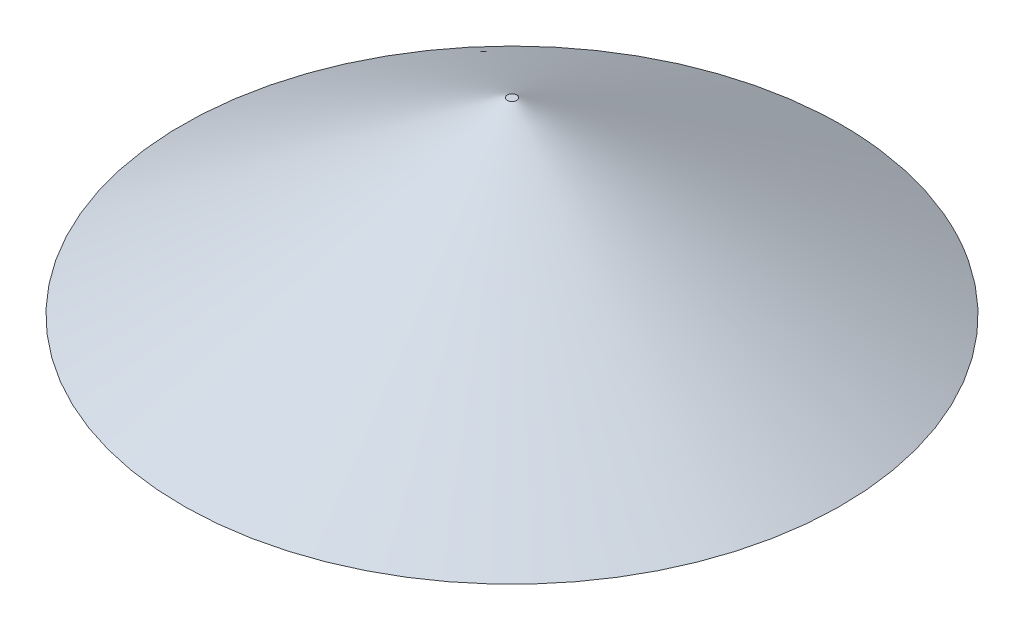
SolidWorks part; units mm, degrees
ref_plane "Front Plane" through (0, 0, 0) normal (0, 0, 1) x (1, 0, 0)
ref_plane "Top Plane" through (0, 0, 0) normal (0, 1, 0) x (1, 0, 0)
ref_plane "Right Plane" through (0, 0, 0) normal (1, 0, 0) x (0, 0, -1)
ref_plane "Plane1" through (0, 20, 0) normal (0, 1, 0) x (1, 0, 0)
sketch "Sketch1" plane through (0, 0, 0) normal (0, 1, 0) x (1, 0, 0)
  circle A0 centre (0, 0) radius 35
  dimension "D1" = 70
sketch "Sketch2" plane through (0, 20, 0) normal (0, 1, 0) x (1, 0, 0)
  circle A0 centre (0, 0) radius 0.5
loft "Loft1" add profiles "Sketch1", "Sketch2" connector at (-9.0681, 0, 33.8049) connector at (0, 20, 0.5)
